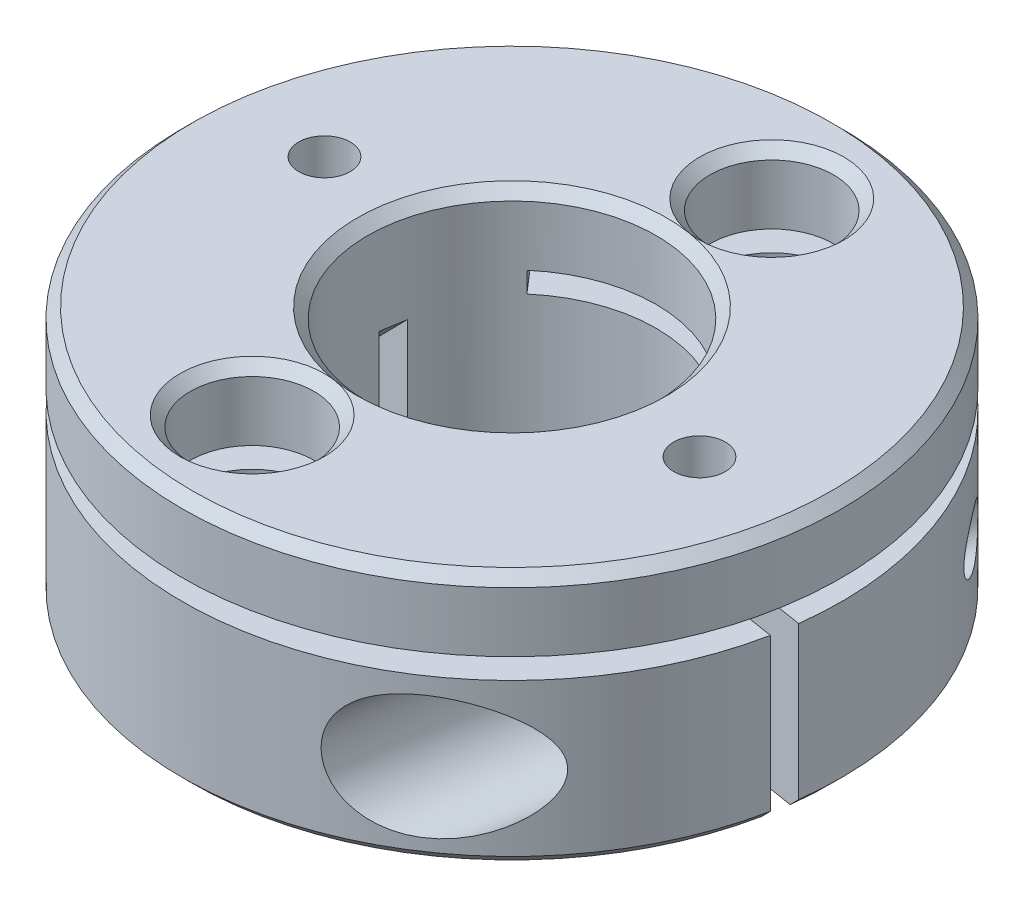
SolidWorks part; units mm, degrees
ref_plane "前视基准面" through (0, 0, 0) normal (0, 0, 1) x (1, 0, 0)
ref_plane "上视基准面" through (0, 0, 0) normal (0, 1, 0) x (1, 0, 0)
ref_plane "右视基准面" through (0, 0, 0) normal (1, 0, 0) x (0, 0, -1)
sketch "草图1" plane through (0, 0, 0) normal (0, 1, 0) x (1, 0, 0)
  circle A0 centre (0, 0) radius 16
  dimension "D1" = 32
extrude "凸台-拉伸1" add sketch "草图1" along normal blind 12.3
sketch "草图2" plane through (0, 12.3, 0) normal (0, 1, 0) x (1, 0, 0)
  line L0 (-2.6148, 3.027) -> (-10.459, 12.1082)
  line L1 (-3.4351, -2.0494) -> (-13.7404, -8.1976)
  circle A0 centre (0, 0) radius 16 construction
  arc A1 (-13.7404, -8.1976) -> (-10.459, 12.1082) centre (0, 0) ccw
  arc A2 (-3.4351, -2.0494) -> (-2.6148, 3.027) centre (0, 0) ccw
  dimension "D1" = 8
  dimension "D2" = 80
extrude "切除-拉伸1" cut sketch "草图2" against normal blind 1 from offset 3.4 offset against normal yes
sketch "草图3" plane through (0, 12.3, 0) normal (0, 1, 0) x (1, 0, 0)
  line L0 (-22.1826, 4.1925) -> (25.6659, -3.5398)
  line L1 (25.6659, -3.5398) -> (25.4745, -4.7244)
  line L2 (25.4745, -4.7244) -> (-22.374, 3.0078)
  line L3 (-22.374, 3.0078) -> (-22.1826, 4.1925)
  line L4 (0, 0) -> (0.0957, 0.5923) construction
  line L5 (-10.459, 12.1082) -> (-2.6148, 3.027) construction
  line L6 (-10.459, 12.1082) -> (-2.6148, 3.027) construction
  dimension "D1" = 1.2
  dimension "D2" = 0.6
  dimension "D3" = 40
extrude "切除-拉伸2" cut sketch "草图3" against normal blind 10 from offset 4 offset against normal yes
sketch "草图4" plane through (-0.0957, 0, 0.5923) normal (0.1595, 0, -0.9872) x (-0.9872, 0, -0.1595)
  line L0 (15.9887, 0) -> (15.9887, 9.0294)
  line L1 (15.9887, 9.0294) -> (5.4593, 9.0294)
  line L2 (5.4593, 9.0294) -> (14.4887, 0)
  line L3 (-15.9887, 0) -> (15.9887, 0) construction
  line L4 (14.4887, 0) -> (15.9887, 0)
  dimension "D1" = 1.5
  dimension "D2" = 45
extrude "凸台-拉伸2" add sketch "草图4" along normal blind 1.2
sketch "草图5" plane through (0, 12.3, 0) normal (0, 1, 0) x (1, 0, 0)
  line L0 (-15.6883, 3.143) -> (-15.8797, 1.9584) construction
  line L1 (-15.6883, 3.143) -> (-15.8797, 1.9584)
  arc A0 (-15.6883, 3.143) -> (-15.8797, 1.9584) centre (0, 0) ccw
extrude "凸台-拉伸3" add sketch "草图5" against normal up to surface (12.3 mm away) up to face at (-4.7677, 0, -0.7705)
sketch "草图6" plane through (0, 12.3, 0) normal (0, 1, 0) x (1, 0, 0)
  circle A0 centre (0, 0) radius 7
  dimension "D1" = 14
extrude "切除-拉伸3" cut sketch "草图6" against normal blind 22.2
sketch "草图7" plane through (0, 0, 0) normal (0, -1, 0) x (1, 0, 0)
  line L0 (0, 0) -> (-1.7548, 10.8591) construction
  line L1 (6.7892, 1.7049) -> (15.6883, 3.143) construction
  circle A0 centre (-1.7548, 10.8591) radius 3
  circle A1 centre (1.7548, -10.8591) radius 3
  point P11 (0, 0)
  dimension "D2" = 6
  dimension "D1" = 11
  dimension "D3" = 2
extrude "切除-拉伸4" cut sketch "草图7" against normal blind 22.2
sketch "草图8" plane through (0, 0, 0) normal (0, -1, 0) x (1, 0, 0)
  line L0 (-10.8591, -1.7548) -> (0, 0) construction
  line L1 (-14.3989, -1.7191) -> (-6.9806, -0.5203) construction
  circle A0 centre (-10.8591, -1.7548) radius 1.25
  circle A1 centre (10.8591, 1.7548) radius 1.25
  point P11 (0, 0)
  dimension "D1" = 2.5
  dimension "D2" = 11
  dimension "D3" = 2
extrude "切除-拉伸5" cut sketch "草图8" against normal blind 22.2
sketch "草图9" plane through (-0.0957, 0, 0.5923) normal (0.1595, 0, -0.9872) x (-0.9872, 0, -0.1595)
  line L0 (-12.0966, 5.7459) -> (-9.9034, 5.7459) construction
  line L2 (-12.0966, 0) -> (-12.0966, 7.9) construction
  line L3 (-9.9034, 7.9) -> (-9.9034, 0) construction
  circle A0 centre (-11, 4.0843) radius 1.25
  point P9 (-11, 5.7459)
  dimension "D1" = 2.5
extrude "切除-拉伸6" cut sketch "草图9" against normal blind 22.2 and the other way blind 22.2
sketch "草图10" plane through (-0.0957, 0, 0.5923) normal (0.1595, 0, -0.9872) x (-0.9872, 0, -0.1595)
  circle A0 centre (-11, 4.0843) radius 3
  dimension "D1" = 6
extrude "切除-拉伸7" cut sketch "草图10" against normal blind 22.2 from offset 4 offset against normal yes
chamfer "倒角1" distance 0.5 angle 45 9 edges at (-15.7951, 0, -2.5525) (0, 12.3, 16) (1.7548, 0, -13.8591) (1.1167, 0, -6.9104) (-1.1167, 0, 6.9104) (-1.7548, 0, 7.8591) (-1.7548, 12.3, 13.8591) (1.7548, 12.3, -7.8591) (0, 12.3, 7)
